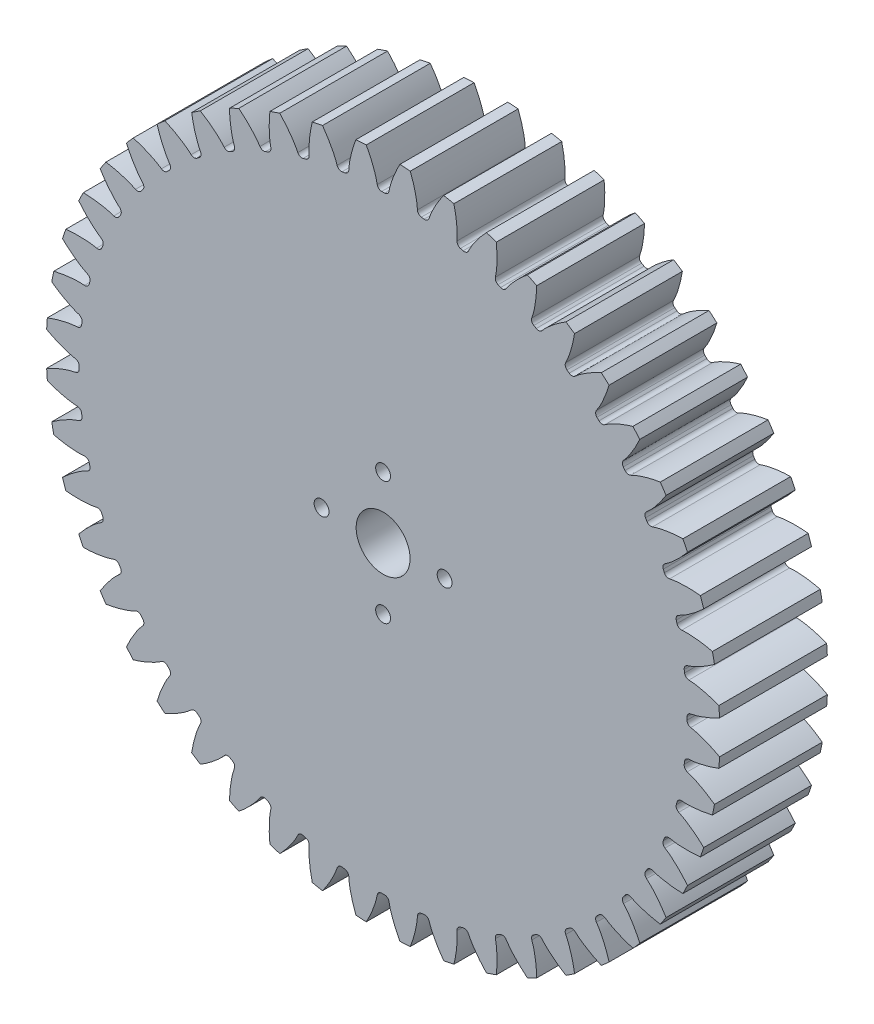
SolidWorks part; units mm, degrees
ref_plane "Front Plane" through (0, 0, 0) normal (0, 0, 1) x (1, 0, 0)
ref_plane "Top Plane" through (0, 0, 0) normal (0, 1, 0) x (1, 0, 0)
ref_plane "Right Plane" through (0, 0, 0) normal (1, 0, 0) x (0, 0, -1)
sketch "Sketch1" plane through (0, 0, 0) normal (0, 0, 1) x (1, 0, 0)
  line L0 (0, 0) -> (0, 38.1) construction
  line L1 (-12.2451, 42.5569) -> (12.2451, 33.6431) construction
  circle A0 centre (0, 0) radius 36.1156 construction
  circle A1 centre (0, 0) radius 39.6875 construction
  circle A2 centre (0, 0) radius 38.1 construction
  circle A3 centre (0, 0) radius 35.8023 construction
  circle A4 centre (0, 0) radius 3.175 construction
  circle A5 centre (0, 0) radius 6.35 construction
  point P8 (203.2, 0)
  point P13 (609.6, 0)
  dimension "OD | Outside Diameter" = 79.375
  dimension "Root Diameter" = 72.2313
  dimension "Gear Pitch Diameter" = 76.2
  dimension "Base Diameter" = 71.6046
  dimension "For Shaft Diameter" = 6.35
  dimension "Hub Diameter" = 12.7
  dimension "Pressure Angle" = 20
  dimension "Number of Teeth" = 1219.2
  dimension "Gear Pitch | Diametral Pitch" = 406.4
sketch "Sketch2" plane through (0, 0, 0) normal (1, 0, 0) x (0, 0, -1)
  line L0 (-6.35, 0) -> (6.35, 0) construction
  line L1 (-6.35, 39.6875) -> (6.35, 39.6875) construction
  point P2 (0, 39.6875)
  point P4 (-5.715, 0)
  point P6 (-5.715, 39.6875)
  dimension "Overall Width" = 12.7
  dimension "Face Width" = 12.065
sketch "Sketch3" plane through (0, 0, 0) normal (0, 0, 1) x (1, 0, 0)
  circle A0 centre (0, 0) radius 39.6875
  circle A1 centre (0, 0) radius 39.6875 construction
extrude "Boss-Extrude1" add sketch "Sketch3" against normal up to vertex (6.35 mm away) and the other way up to vertex (6.35 mm away) up to point (0, 0, -6.35) other way up to point (0, 0, 6.35)
sketch "Sketch4" plane through (0, 0, 0) normal (0, 0, 1) x (1, 0, 0)
  line L0 (0, 0) -> (35.7965, 0.638) construction
  line L2 (0, 0) -> (35.7965, -0.638) construction
  line L4 (35.7965, 0.638) -> (35.7966, 0.638)
  line L5 (35.7966, -0.638) -> (35.7965, -0.638)
  arc A0 (35.7965, 0.638) -> (35.7965, -0.638) centre (0, 0) cw
  arc A3 (39.6379, 1.9832) -> (39.6379, -1.9832) centre (0, 0) cw
  circle A4 centre (0, 0) radius 39.6875 construction
  spline S0 degree 4 poles (35.7966, 0.638) (35.8027, 0.6382) (35.8196, 0.6388) (35.8517, 0.6408) (35.904, 0.6452) (35.9707, 0.6523) (36.0567, 0.6632) (36.1581, 0.6785) (36.2693, 0.6976) (36.3903, 0.7211) (36.5108, 0.7468) (36.631, 0.7746) (36.7506, 0.8043) (36.8954, 0.8425) (37.0688, 0.8916) (37.2712, 0.9536) (37.5005, 1.0294) (37.7337, 1.1125) (37.9629, 1.1992) (38.1941, 1.2923) (38.4174, 1.3864) (38.649, 1.4898) (38.8625, 1.5882) (39.1012, 1.7047) (39.2937, 1.8006) (39.5471, 1.9338) (39.6965, 2.0146) (39.8712, 2.1113) (39.9487, 2.1555) (39.9964, 2.1827) knots 0 0 0 0 0 0.005377 0.015084 0.028532 0.04661 0.064855 0.092111 0.119476 0.146842 0.174209 0.201575 0.228941 0.256307 0.307035 0.361767 0.4165 0.471232 0.525964 0.580697 0.635429 0.690161 0.744894 0.799626 0.854358 0.909091 0.954545 1 1 1 1 1 construction
  spline S1 degree 4 poles (35.7966, 0.638) (35.8027, 0.6382) (35.8196, 0.6388) (35.8517, 0.6408) (35.904, 0.6452) (35.9707, 0.6523) (36.0567, 0.6632) (36.1581, 0.6785) (36.2693, 0.6976) (36.3903, 0.7211) (36.5108, 0.7468) (36.631, 0.7746) (36.7506, 0.8043) (36.8954, 0.8425) (37.0688, 0.8916) (37.2712, 0.9536) (37.5005, 1.0294) (37.7337, 1.1125) (37.9629, 1.1992) (38.1941, 1.2923) (38.4174, 1.3864) (38.649, 1.4898) (38.8625, 1.5882) (39.1012, 1.7047) (39.2937, 1.8006) (39.4921, 1.905) (39.5886, 1.9565) (39.6379, 1.9832) knots 0 0 0 0 0 0.005377 0.015084 0.028532 0.04661 0.064855 0.092111 0.119476 0.146842 0.174209 0.201575 0.228941 0.256307 0.307035 0.361767 0.4165 0.471232 0.525964 0.580697 0.635429 0.690161 0.744894 0.799626 0.854358 0.909091 0.909091 0.909091 0.909091 0.909091
  spline S2 degree 4 poles (35.7966, -0.638) (35.8027, -0.6382) (35.8196, -0.6388) (35.8517, -0.6408) (35.904, -0.6452) (35.9707, -0.6523) (36.0567, -0.6632) (36.1581, -0.6785) (36.2693, -0.6976) (36.3903, -0.7211) (36.5108, -0.7468) (36.631, -0.7746) (36.7506, -0.8043) (36.8954, -0.8425) (37.0688, -0.8916) (37.2712, -0.9536) (37.5005, -1.0294) (37.7337, -1.1125) (37.9629, -1.1992) (38.1941, -1.2923) (38.4174, -1.3864) (38.649, -1.4898) (38.8625, -1.5882) (39.1012, -1.7047) (39.2937, -1.8006) (39.5471, -1.9338) (39.6965, -2.0146) (39.8712, -2.1113) (39.9487, -2.1555) (39.9964, -2.1827) knots 0 0 0 0 0 0.005377 0.015084 0.028532 0.04661 0.064855 0.092111 0.119476 0.146842 0.174209 0.201575 0.228941 0.256307 0.307035 0.361767 0.4165 0.471232 0.525964 0.580697 0.635429 0.690161 0.744894 0.799626 0.854358 0.909091 0.954545 1 1 1 1 1 construction
  spline S3 degree 4 poles (35.7966, -0.638) (35.8027, -0.6382) (35.8196, -0.6388) (35.8517, -0.6408) (35.904, -0.6452) (35.9707, -0.6523) (36.0567, -0.6632) (36.1581, -0.6785) (36.2693, -0.6976) (36.3903, -0.7211) (36.5108, -0.7468) (36.631, -0.7746) (36.7506, -0.8043) (36.8954, -0.8425) (37.0688, -0.8916) (37.2712, -0.9536) (37.5005, -1.0294) (37.7337, -1.1125) (37.9629, -1.1992) (38.1941, -1.2923) (38.4174, -1.3864) (38.649, -1.4898) (38.8625, -1.5882) (39.1012, -1.7047) (39.2937, -1.8006) (39.4921, -1.905) (39.5886, -1.9565) (39.6379, -1.9832) knots 0 0 0 0 0 0.005377 0.015084 0.028532 0.04661 0.064855 0.092111 0.119476 0.146842 0.174209 0.201575 0.228941 0.256307 0.307035 0.361767 0.4165 0.471232 0.525964 0.580697 0.635429 0.690161 0.744894 0.799626 0.854358 0.909091 0.909091 0.909091 0.909091 0.909091
  dimension "D1" = 71.6043
extrude "Cut-Extrude1" cut sketch "Sketch4" against normal through all both and the other way through all
fillet "Fillet1" radius 0.5326 2 edges at (35.7965, -0.638, 0) (35.7965, 0.638, 0)
pattern_circular "CirPattern1" count 48 over 360 about axis through (0, 0, 6.35) along (0, 0, -1) of "Cut-Extrude1", "Fillet1"
sketch "Sketch6" plane through (0, 0, 0) normal (0, 1, 0) x (1, 0, 0)
  line L0 (0, 10.0524) -> (0, -11.762) construction
sketch "Sketch7" plane through (0, 0, 0) normal (0, 0, 1) x (1, 0, 0)
  circle A0 centre (7.25, 0) radius 0.877
  dimension "D2" = 1.754
  dimension "D1" = 7.25
extrude "Cut-Extrude2" cut sketch "Sketch7" against normal through all both and the other way through all
pattern_circular "CirPattern2" count 4 over 360 about axis through (0, 0, -10.0524) along (0, 0, 1) of "Cut-Extrude2"
sketch "Sketch8" plane through (0, 0, 6.35) normal (0, 0, 1) x (1, 0, 0)
  circle A0 centre (0, 0) radius 3.175
  dimension "D1" = 6.35
extrude "Cut-Extrude3" cut sketch "Sketch8" against normal through all
equation "\"Root Diameter@Sketch1\"=\"Root Diameter\""
equation "\"OD | Outside Diameter@Sketch1\"=\"Outside Diameter\""
equation "\"D1@CirPattern1\"=\"Number of Teeth\""
equation "\"Diametral Pitch\"= 16"
equation "\"Number of Teeth\"= 48"
equation "\"Pressure Angle\"=20"
equation "\"Pitch Diameter\"= \"Number of Teeth\" / \"Diametral Pitch\""
equation "\"Base Diameter\"= \"Pitch Diameter\" * cos ( \"Pressure Angle\" )"
equation "\"Outside Diameter\"= ( \"Number of Teeth\" + 2 ) / \"Diametral Pitch\""
equation "\"Dedendum\"= 1.25 / \"Diametral Pitch\""
equation "\"Root Diameter\"= \"Pitch Diameter\" - ( 2 * \"Dedendum\" )"
equation "\"Pitch Angle\"= 360deg / \"Number of Teeth\""
equation "\"Alpha\"= sqr ( \"Pitch Diameter\" ^ 2 - \"Base Diameter\" ^ 2 ) / \"Base Diameter\" * 180 / PI - \"Pressure Angle\""
equation "\"Beta\"= ( \"Pitch Angle\" / 4 - \"Alpha\" )"
equation "\"Phi\"= sqr ( ( \"Outside Diameter\" / 2 ) ^ 2 - ( \"Base Diameter\" / 2 ) ^ 2 ) / ( \"Base Diameter\" / 2 )"
equation "\"Addendum\"= 1 / \"Diametral Pitch\""
equation "\"WorkingDepth\"= 2 / \"Diametral Pitch\""
equation "\"WholeDepth\"= 2.25 / \"Diametral Pitch\""
equation "\"Clearance\"= 0.25 / \"Diametral Pitch\""
equation "\"ToothThickness\"= ( pi * 2 ) / \"Diametral Pitch\""
equation "\"CircularPitch\"= pi / \"Diametral Pitch\""
equation "\"Number of Teeth@Sketch1\"=\"Number of Teeth\""
equation "\"Gear Pitch | Diametral Pitch@Sketch1\"=\"Diametral Pitch\""
equation "\"Pressure Angle@Sketch1\"=\"Pressure Angle\""
equation "\"Gear Pitch Diameter@Sketch1\"=\"Pitch Diameter\""
equation "\"Base Diameter@Sketch1\"=\"Base Diameter\""
equation "\"Fillet\"= \"Clearance\" * cos ( \"Pressure Angle\" ) * tan ( ( 90 + \"Pressure Angle\" ) / 2 )"
equation "\"D1@Fillet1\"=\"Fillet\""
equation "\"D1@Sketch4\"=if( \"Base Diameter\">\"Root Diameter\",\"Root Diameter\",\"Base Diameter\"-.00001)"
equation "\"D1@Fillet2\"=\"Fillet\""
equation "\"D1@Sketch7\"=7.25mm"
equation "\"D2@Sketch7\" = 1.5mm + \"normTol\""
equation "\"tightTol\" = 0.005in"
equation "\"normTol\"= 0.01in"
equation "\"looseTol\"= 0.02in"
